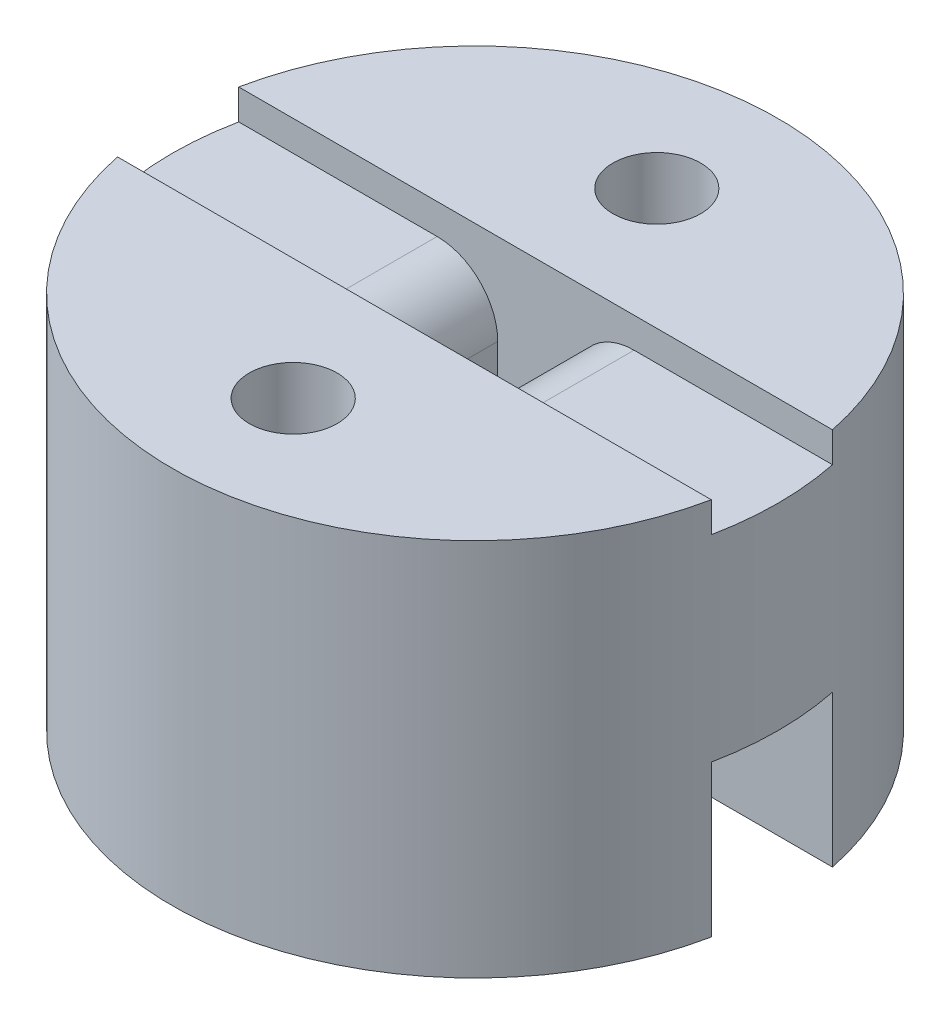
SolidWorks part; units mm, degrees
ref_plane "Front Plane" through (0, 0, 0) normal (0, 0, 1) x (1, 0, 0)
ref_plane "Top Plane" through (0, 0, 0) normal (0, 1, 0) x (1, 0, 0)
ref_plane "Right Plane" through (0, 0, 0) normal (1, 0, 0) x (0, 0, -1)
sketch "Sketch1" plane through (0, 0, 0) normal (0, 1, 0) x (1, 0, 0)
  circle A0 centre (0, 0) radius 20
  dimension "D1" = 40
extrude "Boss-Extrude1" add sketch "Sketch1" along normal blind 25
sketch "Sketch2" plane through (0, 25, 0) normal (0, 1, 0) x (1, 0, 0)
  line L0 (20, 0) -> (0, 0) construction
  line L1 (-20, 4) -> (20, 4)
  line L2 (-20, 4) -> (-20, -4)
  line L3 (-20, -4) -> (20, -4)
  line L4 (20, 4) -> (20, -4)
  circle A0 centre (0, 0) radius 20 construction
  point P6 (0, 0)
  dimension "D1" = 8
extrude "Cut-Extrude1" cut sketch "Sketch2" against normal blind 2
sketch "Sketch3" plane through (0, 25, 0) normal (0, 1, 0) x (1, 0, 0)
  line L0 (0, 0) -> (0, 12) construction
  line L3 (0, 0) -> (0, -12) construction
  dimension "D1" = 12
hole_wizard "M5 Clearance Hole1" positions "3DSketch1" profile "Sketch4" hole size "M5" standard "ANSI Metric" end condition through all
sketch3d "3DSketch1"
  point P0 (0, 25, -12)
  point P3 (0, 25, 12)
sketch "Sketch4" plane through (0, 25, -12) normal (1, 0, 0) x (0, 0, 1)
  line L0 (0, 0) -> (0, 25)
  line L1 (0, 25) -> (2.9, 25)
  line L2 (2.9, 25) -> (2.9, 0)
  line L5 (2.9, 0) -> (0, 0)
  line L11 (0, -6.35) -> (0, 107.95) construction
  dimension "Thru Hole Dia." = 5.8
  dimension "Thru Hole Depth" = 25
sketch "Sketch5" plane through (0, 0, 0) normal (0, -1, 0) x (1, 0, 0)
  line L1 (4.9075, 12) -> (2.4537, 16.25)
  line L2 (2.4537, 16.25) -> (-2.4537, 16.25)
  line L3 (-2.4537, 16.25) -> (-4.9075, 12)
  line L4 (-4.9075, 12) -> (-2.4537, 7.75)
  line L5 (-2.4537, 7.75) -> (2.4537, 7.75)
  line L6 (2.4537, 7.75) -> (4.9075, 12)
  line L7 (4.9075, -12) -> (2.4537, -7.75)
  line L8 (2.4537, -7.75) -> (-2.4537, -7.75)
  line L9 (-2.4537, -7.75) -> (-4.9075, -12)
  line L10 (-4.9075, -12) -> (-2.4537, -16.25)
  line L11 (-2.4537, -16.25) -> (2.4537, -16.25)
  line L12 (2.4537, -16.25) -> (4.9075, -12)
  circle A0 centre (0, 12) radius 4.25 construction
  circle A1 centre (0, -12) radius 4.25 construction
  dimension "D1" = 8.5
extrude "Cut-Extrude2" cut sketch "Sketch5" against normal blind 6
sketch "Sketch6" plane through (0, 23, 0) normal (0, 1, 0) x (1, 0, 0)
  line L0 (19.5959, 4) -> (-19.5959, 4) construction
  line L1 (-2.5, 4) -> (2.5, 4)
  line L2 (-2.5, 4) -> (-2.5, -4)
  line L3 (-2.5, -4) -> (2.5, -4)
  line L4 (2.5, 4) -> (2.5, -4)
  line L5 (-19.5959, -4) -> (19.5959, -4) construction
  point P8 (0, 4)
  dimension "D1" = 5
extrude "Cut-Extrude3" cut sketch "Sketch6" against normal through all both and the other way through all
sketch "Sketch7" plane through (0, 0, 0) normal (0, -1, 0) x (1, 0, 0)
  line L0 (-20, -4) -> (-20, 4) construction
  line L1 (20, -4) -> (20, 4) construction
  line L2 (-20, -4) -> (20, -4) construction
  line L3 (-20, 4) -> (20, 4) construction
  line L4 (-20, -4) -> (-20, 4)
  line L5 (20, -4) -> (20, 4)
  line L6 (-20, -4) -> (20, -4)
  line L7 (-20, 4) -> (20, 4)
extrude "Cut-Extrude4" cut sketch "Sketch7" against normal blind 10
fillet "Fillet1" radius 4 4 edges at (-2.5, 23, 0) (2.5, 23, 0) (-2.5, 10, 0) (2.5, 10, 0)
